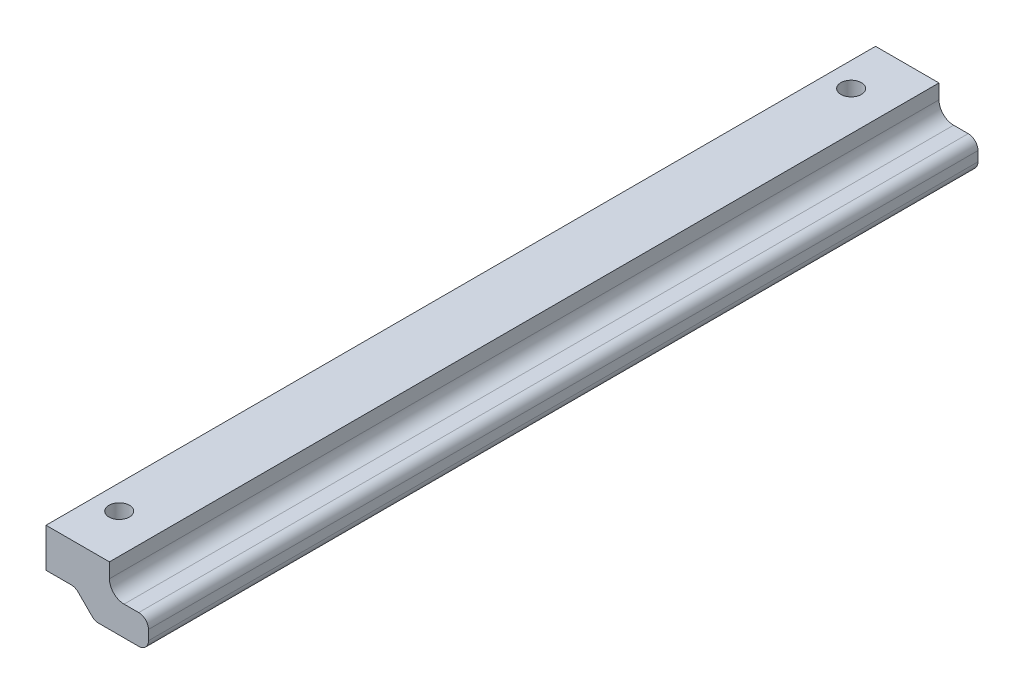
SolidWorks part; units mm, degrees
ref_plane "Front Plane" through (0, 0, 0) normal (0, 0, 1) x (1, 0, 0)
ref_plane "Top Plane" through (0, 0, 0) normal (0, 1, 0) x (1, 0, 0)
ref_plane "Right Plane" through (0, 0, 0) normal (1, 0, 0) x (0, 0, -1)
sketch "Sketch1" plane through (0, 0, 0) normal (0, 0, 1) x (1, 0, 0)
  line L1 (13, -6) -> (13, 0)
  line L2 (55, 0) -> (-55, 0) construction
  line L6 (13, -6) -> (21, -6)
  line L7 (21, -6) -> (21, -12)
  line L8 (0, 0) -> (13, 0)
  line L9 (21, -12) -> (10, -12)
  line L10 (10, -12) -> (6, -8)
  line L11 (6, -8) -> (0, -8)
  line L13 (0, -55) -> (0, 55) construction
  line L14 (0, -8) -> (0, 0)
  dimension "D1" = 6
  dimension "D2" = 6
  dimension "D3" = 8
  dimension "D4" = 10
  dimension "D5" = 8
  dimension "D6" = 45
extrude "Boss-Extrude1" add sketch "Sketch1" against normal blind 170 contours L7 L6 region at (9.8798, -6.062, 0)
fillet "Fillet2" radius 3 1 edges at (13, -6, -85)
sketch "Sketch2" plane through (0, 0, 0) normal (0, 1, 0) x (1, 0, 0)
  line L0 (0, -6.6) -> (0, 6.6) construction
  line L1 (-6.6, 0) -> (6.6, 0) construction
  circle A0 centre (5, 10) radius 2.1
  circle A1 centre (5, 160) radius 2.1
  dimension "D3" = 4.2
  dimension "D1" = 5
  dimension "D2" = 10
  dimension "D4" = 150
extrude "Cut-Extrude1" cut sketch "Sketch2" against normal up to surface (8 mm away) up to face at (3, -8, -85)
sketch "Sketch3" plane through (0, 0, 0) normal (0, 1, 0) x (1, 0, 0)
  line L0 (0, -6.6) -> (0, 6.6) construction
  line L1 (1.55, 11.9919) -> (1.55, 8.0081)
  line L16 (1.55, 8.0081) -> (5, 6.0163)
  line L17 (5, 6.0163) -> (8.45, 8.0081)
  line L18 (8.45, 8.0081) -> (8.45, 11.9919)
  line L19 (8.45, 11.9919) -> (5, 13.9837)
  line L20 (5, 13.9837) -> (1.55, 11.9919)
  line L22 (1.55, 161.9919) -> (1.55, 158.0081)
  line L23 (1.55, 158.0081) -> (5, 156.0163)
  line L24 (5, 156.0163) -> (8.45, 158.0081)
  line L25 (8.45, 158.0081) -> (8.45, 161.9919)
  line L26 (8.45, 161.9919) -> (5, 163.9837)
  line L27 (5, 163.9837) -> (1.55, 161.9919)
  circle A2 centre (5, 10) radius 3.45 construction
  circle A3 centre (5, 160) radius 3.45 construction
  dimension "D1" = 6.9
  dimension "D2" = 6.9
extrude "Cut-Extrude2" cut sketch "Sketch3" along normal offset from surface (9 mm away) 3 from surface up to face at (5, 0, -7.9) starting at face at (15.5, -12, -85)
fillet "Fillet3" radius 2 2 edges at (21, -12, -85) (21, -6, -85)
sketch "Sketch4" plane through (0, 0, 0) normal (-1, 0, 0) x (0, 0, 1)
  line L0 (-170, 0) -> (0, 0) construction
  line L1 (-41.4426, 0) -> (-33.4426, 0)
  line L2 (-41.4426, 0) -> (-41.4426, -5)
  line L3 (-41.4426, -5) -> (-33.4426, -5)
  line L4 (-33.4426, 0) -> (-33.4426, -5)
  dimension "D1" = 5
  dimension "D2" = 8
extrude "Cut-Extrude3" [suppressed] cut sketch "Sketch4" against normal up to surface (21 mm away) up to face at (21, -9, -85)
fillet "Fillet4" radius 2 4 edges at (6, -8, -166.7032) (6, -8, -85) (10, -12, -85) (6, -8, -3.2968)
